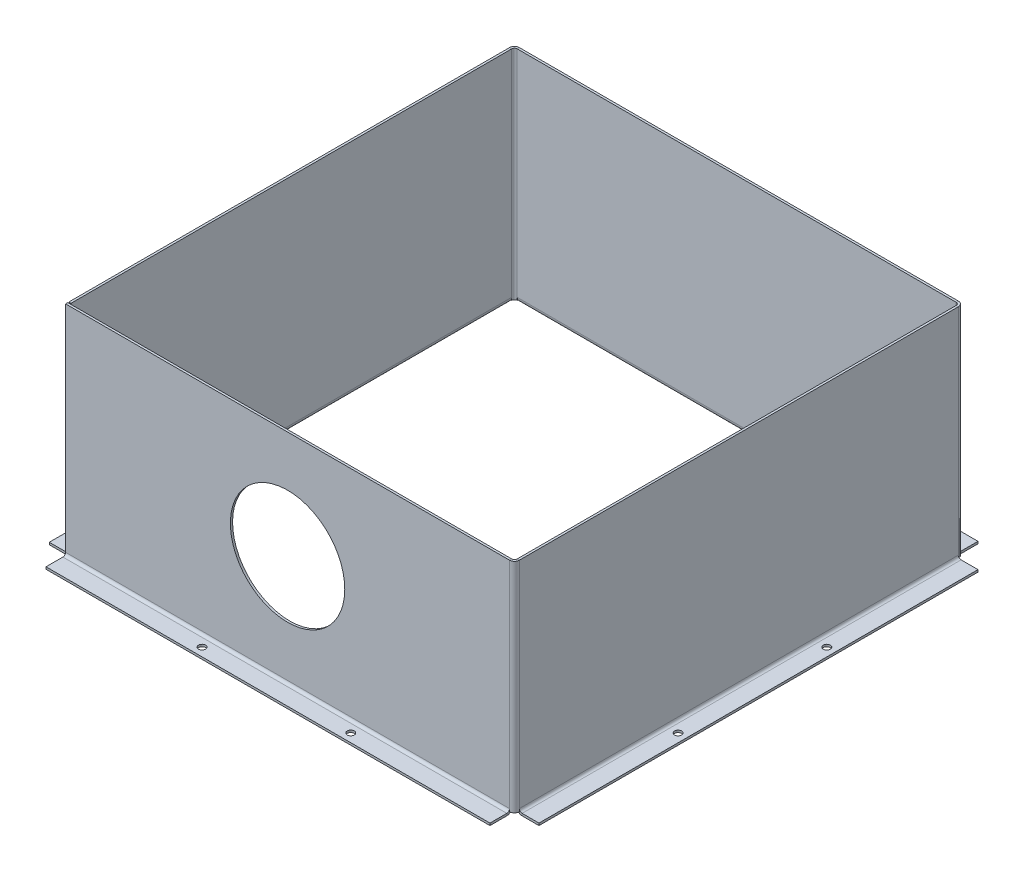
SolidWorks part; units mm, degrees
note: The reader was unsure of these and kept them because the rebuilt part matched: flange length of "Edge-Flange2", "Edge-Flange4", "Edge-Flange5", "Edge-Flange6", "Edge-Flange7", "Edge-Flange8", "Edge-Flange9".
material "Galvanized Steel"
ref_plane "Front Plane" through (0, 0, 0) normal (0, 0, 1) x (1, 0, 0)
ref_plane "Top Plane" through (0, 0, 0) normal (0, 1, 0) x (1, 0, 0)
ref_plane "Right Plane" through (0, 0, 0) normal (1, 0, 0) x (0, 0, -1)
sketch "Sketch1" plane through (0, 0, 0) normal (0, 0, 1) x (1, 0, 0)
  line L1 (190.5051, 103.0177) -> (-219.4949, 103.0177)
  line L2 (190.5051, 103.0177) -> (190.5051, -96.9823)
  line L3 (190.5051, -96.9823) -> (-219.4949, -96.9823)
  line L4 (-219.4949, 103.0177) -> (-219.4949, -96.9823)
  dimension "D1" = 410
  dimension "D2" = 200
base flange "Base-Flange1" sketch "Sketch1" thickness 2 reverse thickness direction no parameters "D1"=0.7366
edge flange "Edge-Flange2" sketch "Sketch9" flange angle 90 flange length 410 flange position material outside bend radius 2.5 thickness 2 relief rectangular parameters "D6"=10
sketch "Sketch9" plane through (190.5051, 0, -2) normal (-1, 0, 0) x (0, 1, 0)
  line L2 (-96.9823, 0) -> (-96.9823, 408)
  line L3 (-96.9823, 408) -> (103.0177, 408)
  line L4 (103.0177, 408) -> (103.0177, 0)
  line L8 (103.0177, 0) -> (-96.9823, 0) construction
  line L9 (103.0177, 0) -> (-96.9823, 0)
bend "EdgeBend1" bend radius 2.5 bend angle 90 parameters "D5"=1
edge flange "Edge-Flange4" sketch "Sketch13" flange angle 90 flange length 410 flange position material outside bend radius 2.5 thickness 2 relief rectangular parameters "D6"=10
sketch "Sketch13" plane through (190.5051, 0, -410) normal (0, 0, 1) x (0, 1, 0)
  line L2 (-96.9823, 0) -> (-96.9823, 408)
  line L3 (-96.9823, 408) -> (103.0177, 408)
  line L4 (103.0177, 408) -> (103.0177, 0)
  line L6 (103.0177, 0) -> (-96.9823, 0) construction
  line L7 (103.0177, 0) -> (-96.9823, 0)
bend "EdgeBend2" bend radius 2.5 bend angle 90 parameters "D5"=2
edge flange "Edge-Flange5" sketch "Sketch16" flange angle 90 flange length 409 flange position material outside bend radius 2.5 thickness 2 relief rectangular parameters "D6"=10
sketch "Sketch16" plane through (-217.4949, 0, -410) normal (1, 0, 0) x (0, 1, 0)
  line L1 (103.0177, 0) -> (-96.9823, 0) construction
  line L2 (-96.9823, 0) -> (-96.9823, 407)
  line L3 (-96.9823, 407) -> (103.0177, 407)
  line L4 (103.0177, 407) -> (103.0177, 0)
  line L5 (103.0177, 0) -> (-96.9823, 0)
bend "EdgeBend3" bend radius 2.5 bend angle 90 parameters "D5"=3
edge flange "Edge-Flange6" sketch "Sketch19" flange angle 90 flange length 20 flange position material outside bend radius 2.5 thickness 2 relief none parameters "D6"=10
sketch "Sketch19" plane through (0, -96.9823, -412) normal (0, 1, 0) x (1, 0, 0)
  line L1 (188.0051, 0) -> (-214.9949, 0) construction
  line L2 (-214.9949, 0) -> (-214.9949, 18)
  line L3 (-214.9949, 18) -> (188.0051, 18)
  line L4 (188.0051, 18) -> (188.0051, 0)
  line L5 (188.0051, 0) -> (-214.9949, 0)
bend "EdgeBend4" bend radius 2.5 bend angle 90 parameters "D5"=4
edge flange "Edge-Flange7" sketch "Sketch22" flange angle 90 flange length 20 flange position material outside bend radius 2.5 thickness 2 relief none parameters "D6"=10
sketch "Sketch22" plane through (192.5051, -96.9823, 0) normal (0, 1, 0) x (0, 0, 1)
  line L2 (-407.5, 0) -> (-407.5, 18)
  line L3 (-407.5, 18) -> (-4.5, 18)
  line L4 (-4.5, 18) -> (-4.5, 0)
  line L6 (-4.5, 0) -> (-407.5, 0) construction
  line L7 (-4.5, 0) -> (-407.5, 0)
bend "EdgeBend5" bend radius 2.5 bend angle 90 parameters "D5"=5
edge flange "Edge-Flange8" sketch "Sketch25" flange angle 90 flange length 20 flange position material outside bend radius 2.5 thickness 2 relief none parameters "D6"=10
sketch "Sketch25" plane through (0, -96.9823, 0) normal (0, 1, 0) x (-1, 0, 0)
  line L1 (219.4949, 0) -> (-188.0051, 0) construction
  line L2 (-188.0051, 0) -> (-188.0051, 18)
  line L3 (-188.0051, 18) -> (219.4949, 18)
  line L4 (219.4949, 18) -> (219.4949, 0)
  line L5 (219.4949, 0) -> (-188.0051, 0)
bend "EdgeBend6" bend radius 2.5 bend angle 90 parameters "D5"=6
edge flange "Edge-Flange9" sketch "Sketch28" flange angle 90 flange length 20 flange position material outside bend radius 2.5 thickness 2 relief none parameters "D6"=10
sketch "Sketch28" plane through (-219.4949, -96.9823, 0) normal (0, 1, 0) x (0, 0, -1)
  line L2 (3, 0) -> (3, 18)
  line L3 (3, 18) -> (407.5, 18)
  line L4 (407.5, 18) -> (407.5, 0)
  line L6 (407.5, 0) -> (3, 0) construction
  line L7 (407.5, 0) -> (3, 0)
bend "EdgeBend7" bend radius 2.5 bend angle 90 parameters "D5"=7
sketch "Sketch29" plane through (0, 0, 0) normal (0, 0, 1) x (1, 0, 0)
  circle A0 centre (-15.7449, 4.2677) radius 52.5
  dimension "D1" = 105
extrude "Cut-Extrude1" cut sketch "Sketch29" against normal blind 10 normal cut yes
sketch "Sketch30" plane through (0, -96.9823, 0) normal (0, 1, 0) x (1, 0, 0)
  line L0 (-219.4949, -2.5) -> (-219.4949, -18) construction
  line L2 (188.0051, -18) -> (188.0051, -2.5) construction
  line L3 (195.0051, 4.5) -> (210.5051, 4.5) construction
  line L4 (188.0051, 414.5) -> (188.0051, 430) construction
  line L5 (-221.9949, 407.5) -> (-237.4949, 407.5) construction
  circle A0 centre (-83.9949, -10.25) radius 3.25
  circle A1 centre (52.5051, -10.25) radius 3.25
  circle A2 centre (202.7551, 140) radius 3.25
  circle A3 centre (202.7551, 276.5) radius 3.25
  circle A4 centre (52.5051, 422.25) radius 3.25
  circle A5 centre (-83.9949, 422.25) radius 3.25
  circle A6 centre (-229.7449, 272) radius 3.25
  circle A7 centre (-229.7449, 135.5) radius 3.25
  point P27 (-229.7449, 407.5)
  dimension "D1" = 135.5
  dimension "D2" = 136.5
  dimension "D3" = 135.5
  dimension "D4" = 135.5
  dimension "D5" = 136.5
  dimension "D6" = 135.5
  dimension "D7" = 136.5
  dimension "D8" = 135.5
  dimension "D9" = 136.5
extrude "Cut-Extrude2" cut sketch "Sketch30" against normal blind 10 normal cut yes
sketch "Bend-Lines1" [suppressed] plane through (0, 0, 0) normal (0, 1, 0) x (1, 0, 0)
sketch "Bounding-Box1" [suppressed] plane through (0, 0, 0) normal (0, 1, 0) x (1, 0, 0)
sheet metal parameters "Sheet-Metal1" thickness 2 parameters "D1"=0.7366
flat pattern "Flat-Pattern1" [suppressed]
sketch "Bend-Lines2" plane through (0, 0, 0) normal (0, 1, 0) x (1, 0, 0)
sketch3d "Bounding-Box2" [suppressed]
  line L0 (219.4949, -96.9823, 0) -> (-190.5051, -96.9823, 0) construction
  line L1 (219.4949, 103.0177, 0) -> (-190.5051, 103.0177, 0) construction
  line L2 (219.4949, -96.9823, 0) -> (219.4949, 103.0177, 0) construction
  line L3 (-190.5051, -96.9823, 0) -> (-190.5051, 103.0177, 0) construction
sheet metal parameters "Sheet-Metal2" thickness 2 parameters "D1"=0.7366
flat pattern "Flat-Pattern1"
sketch "Bend-Lines2" plane through (0, 0, 0) normal (0, 0, 1) x (1, 0, 0)
  line L0 (190.7539, -96.9823) -> (190.7539, 103.0177) construction
  line L1 (190.7539, -96.9823) -> (190.7539, 103.0177) construction
sketch3d "Bounding-Box2" [suppressed]
  line L0 (-219.4949, -96.9823, 0) -> (599.0028, -96.9823, 0) construction
  line L1 (-219.4949, 103.0177, 0) -> (599.0028, 103.0177, 0) construction
  line L2 (-219.4949, -96.9823, 0) -> (-219.4949, 103.0177, 0) construction
  line L3 (599.0028, -96.9823, 0) -> (599.0028, 103.0177, 0) construction
bend of the flat pattern "Flatten-<EdgeBend1>1"
sheet metal parameters "Sheet-Metal3" thickness 2 parameters "D1"=0.7366
flat pattern "Flat-Pattern1"
sketch "Bend-Lines2" plane through (0, 0, 0) normal (0, 0, 1) x (1, 0, 0)
  line L0 (190.7539, -96.9823) -> (190.7539, 103.0177) construction
  line L1 (190.7539, -96.9823) -> (190.7539, 103.0177) construction
  line L2 (599.2517, -96.9823) -> (599.2517, 103.0177) construction
  line L3 (599.2517, -96.9823) -> (599.2517, 103.0177) construction
sketch3d "Bounding-Box2" [suppressed]
  line L0 (-219.4949, -96.9823, 0) -> (1007.5006, -96.9823, 0) construction
  line L1 (-219.4949, 103.0177, 0) -> (1007.5006, 103.0177, 0) construction
  line L2 (-219.4949, -96.9823, 0) -> (-219.4949, 103.0177, 0) construction
  line L3 (1007.5006, -96.9823, 0) -> (1007.5006, 103.0177, 0) construction
bend of the flat pattern "Flatten-<EdgeBend1>1"
bend of the flat pattern "Flatten-<EdgeBend2>1"
sheet metal parameters "Sheet-Metal4" thickness 2 parameters "D1"=0.7366
flat pattern "Flat-Pattern1"
sketch "Bend-Lines2" plane through (0, 0, 0) normal (0, 0, 1) x (1, 0, 0)
  line L0 (190.7539, -96.9823) -> (190.7539, 103.0177) construction
  line L1 (190.7539, -96.9823) -> (190.7539, 103.0177) construction
  line L2 (599.2517, -96.9823) -> (599.2517, 103.0177) construction
  line L3 (599.2517, -96.9823) -> (599.2517, 103.0177) construction
  line L4 (1007.7495, -96.9823) -> (1007.7495, 103.0177) construction
  line L5 (1007.7495, -96.9823) -> (1007.7495, 103.0177) construction
sketch3d "Bounding-Box2" [suppressed]
  line L0 (-219.4949, -96.9823, 0) -> (1414.9984, -96.9823, 0) construction
  line L1 (-219.4949, 103.0177, 0) -> (1414.9984, 103.0177, 0) construction
  line L2 (-219.4949, -96.9823, 0) -> (-219.4949, 103.0177, 0) construction
  line L3 (1414.9984, -96.9823, 0) -> (1414.9984, 103.0177, 0) construction
bend of the flat pattern "Flatten-<EdgeBend1>1"
bend of the flat pattern "Flatten-<EdgeBend2>1"
bend of the flat pattern "Flatten-<EdgeBend3>1"
sheet metal parameters "Sheet-Metal5" thickness 2 parameters "D1"=0.7366
flat pattern "Flat-Pattern1"
sketch "Bend-Lines2" plane through (0, 0, 0) normal (0, 0, 1) x (1, 0, 0)
  line L0 (190.7539, -96.9823) -> (190.7539, 103.0177) construction
  line L1 (190.7539, -96.9823) -> (190.7539, 103.0177) construction
  line L2 (599.2517, -96.9823) -> (599.2517, 103.0177) construction
  line L3 (599.2517, -96.9823) -> (599.2517, 103.0177) construction
  line L4 (1007.7495, -96.9823) -> (1007.7495, 103.0177) construction
  line L5 (1007.7495, -96.9823) -> (1007.7495, 103.0177) construction
  line L6 (602.0006, -97.2312) -> (1005.0006, -97.2312) construction
  line L7 (602.0006, -97.2312) -> (1005.0006, -97.2312) construction
sketch3d "Bounding-Box2" [suppressed]
  line L0 (-219.4949, -115.4801, 0) -> (1414.9984, -115.4801, 0) construction
  line L1 (-219.4949, 103.0177, 0) -> (1414.9984, 103.0177, 0) construction
  line L2 (-219.4949, -115.4801, 0) -> (-219.4949, 103.0177, 0) construction
  line L3 (1414.9984, -115.4801, 0) -> (1414.9984, 103.0177, 0) construction
bend of the flat pattern "Flatten-<EdgeBend1>1"
bend of the flat pattern "Flatten-<EdgeBend2>1"
bend of the flat pattern "Flatten-<EdgeBend3>1"
bend of the flat pattern "Flatten-<EdgeBend4>1"
sheet metal parameters "Sheet-Metal6" thickness 2 parameters "D1"=0.7366
flat pattern "Flat-Pattern1"
sketch "Bend-Lines2" plane through (0, 0, 0) normal (0, 0, 1) x (1, 0, 0)
  line L0 (190.7539, -96.9823) -> (190.7539, 103.0177) construction
  line L1 (190.7539, -96.9823) -> (190.7539, 103.0177) construction
  line L2 (599.2517, -96.9823) -> (599.2517, 103.0177) construction
  line L3 (599.2517, -96.9823) -> (599.2517, 103.0177) construction
  line L4 (1007.7495, -96.9823) -> (1007.7495, 103.0177) construction
  line L5 (1007.7495, -96.9823) -> (1007.7495, 103.0177) construction
  line L6 (602.0006, -97.2312) -> (1005.0006, -97.2312) construction
  line L7 (602.0006, -97.2312) -> (1005.0006, -97.2312) construction
  line L8 (193.5028, -97.2312) -> (596.5028, -97.2312) construction
  line L9 (193.5028, -97.2312) -> (596.5028, -97.2312) construction
sketch3d "Bounding-Box2" [suppressed]
  line L0 (-219.4949, -115.4801, 0) -> (1414.9984, -115.4801, 0) construction
  line L1 (-219.4949, 103.0177, 0) -> (1414.9984, 103.0177, 0) construction
  line L2 (-219.4949, -115.4801, 0) -> (-219.4949, 103.0177, 0) construction
  line L3 (1414.9984, -115.4801, 0) -> (1414.9984, 103.0177, 0) construction
bend of the flat pattern "Flatten-<EdgeBend1>1"
bend of the flat pattern "Flatten-<EdgeBend2>1"
bend of the flat pattern "Flatten-<EdgeBend3>1"
bend of the flat pattern "Flatten-<EdgeBend4>1"
bend of the flat pattern "Flatten-<EdgeBend5>1"
sheet metal parameters "Sheet-Metal7" thickness 2 parameters "D1"=0.7366
flat pattern "Flat-Pattern1"
sketch "Bend-Lines2" plane through (0, 0, 0) normal (0, 0, 1) x (1, 0, 0)
  line L0 (190.7539, -96.9823) -> (190.7539, 103.0177) construction
  line L1 (190.7539, -96.9823) -> (190.7539, 103.0177) construction
  line L2 (599.2517, -96.9823) -> (599.2517, 103.0177) construction
  line L3 (599.2517, -96.9823) -> (599.2517, 103.0177) construction
  line L4 (1007.7495, -96.9823) -> (1007.7495, 103.0177) construction
  line L5 (1007.7495, -96.9823) -> (1007.7495, 103.0177) construction
  line L6 (602.0006, -97.2312) -> (1005.0006, -97.2312) construction
  line L7 (602.0006, -97.2312) -> (1005.0006, -97.2312) construction
  line L8 (193.5028, -97.2312) -> (596.5028, -97.2312) construction
  line L9 (193.5028, -97.2312) -> (596.5028, -97.2312) construction
  line L10 (-219.4949, -97.2312) -> (188.0051, -97.2312) construction
  line L11 (-219.4949, -97.2312) -> (188.0051, -97.2312) construction
sketch3d "Bounding-Box2" [suppressed]
  line L0 (-219.4949, -115.4801, 0) -> (1414.9984, -115.4801, 0) construction
  line L1 (-219.4949, 103.0177, 0) -> (1414.9984, 103.0177, 0) construction
  line L2 (-219.4949, -115.4801, 0) -> (-219.4949, 103.0177, 0) construction
  line L3 (1414.9984, -115.4801, 0) -> (1414.9984, 103.0177, 0) construction
bend of the flat pattern "Flatten-<EdgeBend1>1"
bend of the flat pattern "Flatten-<EdgeBend2>1"
bend of the flat pattern "Flatten-<EdgeBend3>1"
bend of the flat pattern "Flatten-<EdgeBend4>1"
bend of the flat pattern "Flatten-<EdgeBend5>1"
bend of the flat pattern "Flatten-<EdgeBend6>1"
sheet metal parameters "Sheet-Metal8" thickness 2 parameters "D1"=0.7366
flat pattern "Flat-Pattern1"
sketch "Bend-Lines2" plane through (0, 0, 0) normal (0, 0, 1) x (1, 0, 0)
  line L0 (190.7539, -96.9823) -> (190.7539, 103.0177) construction
  line L1 (190.7539, -96.9823) -> (190.7539, 103.0177) construction
  line L2 (599.2517, -96.9823) -> (599.2517, 103.0177) construction
  line L3 (599.2517, -96.9823) -> (599.2517, 103.0177) construction
  line L4 (1007.7495, -96.9823) -> (1007.7495, 103.0177) construction
  line L5 (1007.7495, -96.9823) -> (1007.7495, 103.0177) construction
  line L6 (602.0006, -97.2312) -> (1005.0006, -97.2312) construction
  line L7 (602.0006, -97.2312) -> (1005.0006, -97.2312) construction
  line L8 (193.5028, -97.2312) -> (596.5028, -97.2312) construction
  line L9 (193.5028, -97.2312) -> (596.5028, -97.2312) construction
  line L10 (-219.4949, -97.2312) -> (188.0051, -97.2312) construction
  line L11 (-219.4949, -97.2312) -> (188.0051, -97.2312) construction
  line L12 (1010.4984, -97.2312) -> (1414.9984, -97.2312) construction
  line L13 (1010.4984, -97.2312) -> (1414.9984, -97.2312) construction
sketch3d "Bounding-Box2" [suppressed]
  line L0 (-219.4949, -115.4801, 0) -> (1414.9984, -115.4801, 0) construction
  line L1 (-219.4949, 103.0177, 0) -> (1414.9984, 103.0177, 0) construction
  line L2 (-219.4949, -115.4801, 0) -> (-219.4949, 103.0177, 0) construction
  line L3 (1414.9984, -115.4801, 0) -> (1414.9984, 103.0177, 0) construction
bend of the flat pattern "Flatten-<EdgeBend1>1"
bend of the flat pattern "Flatten-<EdgeBend2>1"
bend of the flat pattern "Flatten-<EdgeBend3>1"
bend of the flat pattern "Flatten-<EdgeBend4>1"
bend of the flat pattern "Flatten-<EdgeBend5>1"
bend of the flat pattern "Flatten-<EdgeBend6>1"
bend of the flat pattern "Flatten-<EdgeBend7>1"
sheet metal parameters "Sheet-Metal9" thickness 2 parameters "D1"=0.7366
flat pattern "Flat-Pattern1"
sketch "Bend-Lines2" plane through (0, 0, 0) normal (0, 0, 1) x (1, 0, 0)
  line L0 (190.7539, -96.9823) -> (190.7539, 103.0177) construction
  line L1 (190.7539, -96.9823) -> (190.7539, 103.0177) construction
  line L2 (599.2517, -96.9823) -> (599.2517, 103.0177) construction
  line L3 (599.2517, -96.9823) -> (599.2517, 103.0177) construction
  line L4 (1007.7495, -96.9823) -> (1007.7495, 103.0177) construction
  line L5 (1007.7495, -96.9823) -> (1007.7495, 103.0177) construction
  line L6 (602.0006, -97.2312) -> (1005.0006, -97.2312) construction
  line L7 (602.0006, -97.2312) -> (1005.0006, -97.2312) construction
  line L8 (193.5028, -97.2312) -> (596.5028, -97.2312) construction
  line L9 (193.5028, -97.2312) -> (596.5028, -97.2312) construction
  line L10 (-219.4949, -97.2312) -> (188.0051, -97.2312) construction
  line L11 (-219.4949, -97.2312) -> (188.0051, -97.2312) construction
  line L12 (1010.4984, -97.2312) -> (1414.9984, -97.2312) construction
  line L13 (1010.4984, -97.2312) -> (1414.9984, -97.2312) construction
sketch3d "Bounding-Box2" [suppressed]
  line L0 (-219.4949, -115.4801, 0) -> (1414.9984, -115.4801, 0) construction
  line L1 (-219.4949, 103.0177, 0) -> (1414.9984, 103.0177, 0) construction
  line L2 (-219.4949, -115.4801, 0) -> (-219.4949, 103.0177, 0) construction
  line L3 (1414.9984, -115.4801, 0) -> (1414.9984, 103.0177, 0) construction
bend of the flat pattern "Flatten-<EdgeBend1>1"
bend of the flat pattern "Flatten-<EdgeBend2>1"
bend of the flat pattern "Flatten-<EdgeBend3>1"
bend of the flat pattern "Flatten-<EdgeBend4>1"
bend of the flat pattern "Flatten-<EdgeBend5>1"
bend of the flat pattern "Flatten-<EdgeBend6>1"
bend of the flat pattern "Flatten-<EdgeBend7>1"
sheet metal parameters "Sheet-Metal10" thickness 2 parameters "D1"=0.7366
flat pattern "Flat-Pattern1"
sketch "Bend-Lines2" plane through (0, 0, 0) normal (0, 0, 1) x (1, 0, 0)
  line L0 (190.7539, -96.9823) -> (190.7539, 103.0177) construction
  line L1 (190.7539, -96.9823) -> (190.7539, 103.0177) construction
  line L2 (599.2517, -96.9823) -> (599.2517, 103.0177) construction
  line L3 (599.2517, -96.9823) -> (599.2517, 103.0177) construction
  line L4 (1007.7495, -96.9823) -> (1007.7495, 103.0177) construction
  line L5 (1007.7495, -96.9823) -> (1007.7495, 103.0177) construction
  line L6 (602.0006, -97.2312) -> (1005.0006, -97.2312) construction
  line L7 (602.0006, -97.2312) -> (1005.0006, -97.2312) construction
  line L8 (193.5028, -97.2312) -> (596.5028, -97.2312) construction
  line L9 (193.5028, -97.2312) -> (596.5028, -97.2312) construction
  line L10 (-219.4949, -97.2312) -> (188.0051, -97.2312) construction
  line L11 (-219.4949, -97.2312) -> (188.0051, -97.2312) construction
  line L12 (1010.4984, -97.2312) -> (1414.9984, -97.2312) construction
  line L13 (1010.4984, -97.2312) -> (1414.9984, -97.2312) construction
sketch3d "Bounding-Box2" [suppressed]
  line L0 (-219.4949, -115.4801, 0) -> (1414.9984, -115.4801, 0) construction
  line L1 (-219.4949, 103.0177, 0) -> (1414.9984, 103.0177, 0) construction
  line L2 (-219.4949, -115.4801, 0) -> (-219.4949, 103.0177, 0) construction
  line L3 (1414.9984, -115.4801, 0) -> (1414.9984, 103.0177, 0) construction
bend of the flat pattern "Flatten-<EdgeBend1>1"
bend of the flat pattern "Flatten-<EdgeBend2>1"
bend of the flat pattern "Flatten-<EdgeBend3>1"
bend of the flat pattern "Flatten-<EdgeBend4>1"
bend of the flat pattern "Flatten-<EdgeBend5>1"
bend of the flat pattern "Flatten-<EdgeBend6>1"
bend of the flat pattern "Flatten-<EdgeBend7>1"
